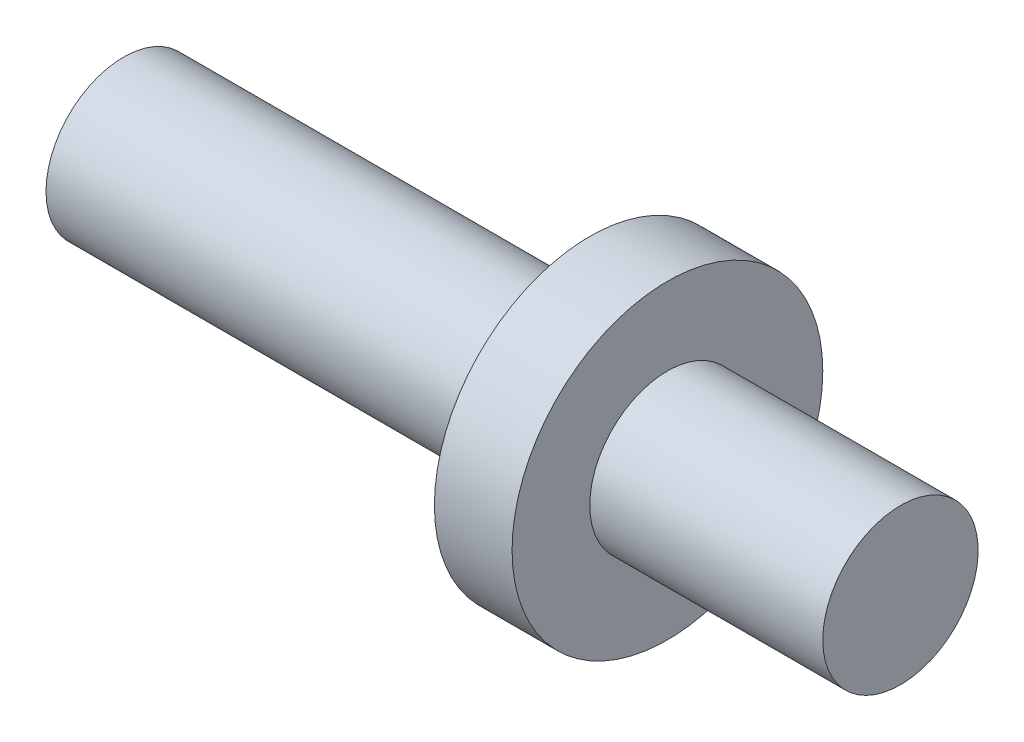
SolidWorks part; units mm, degrees
material "ALUMINUM 6061"
ref_plane "Front Plane" through (0, 0, 0) normal (0, 0, 1) x (1, 0, 0)
ref_plane "Top Plane" through (0, 0, 0) normal (0, 1, 0) x (1, 0, 0)
ref_plane "Right Plane" through (0, 0, 0) normal (1, 0, 0) x (0, 0, -1)
sketch "Sketch1" plane through (0, 0, 0) normal (0, 0, 1) x (1, 0, 0)
  line L0 (0, 0) -> (12.7, 0)
  line L1 (12.7, 0) -> (12.7, 3.175)
  line L2 (12.7, 3.175) -> (3.175, 3.175)
  line L3 (3.175, 3.175) -> (3.175, 6.35)
  line L4 (3.175, 6.35) -> (0, 6.35)
  line L5 (0, 6.35) -> (0, 3.175)
  line L6 (0, 3.175) -> (-19.05, 3.175)
  line L7 (-19.05, 3.175) -> (-19.05, 0)
  line L8 (-19.05, 0) -> (0, 0)
  line L9 (0, 0) -> (0, 3.175) construction
  dimension "D1" = 9.525
  dimension "pinRadius" = 3.175
  dimension "D2" = 19.05
  dimension "D3" = 3.175
  dimension "D4" = 6.35
revolve "Revolve1" add sketch "Sketch1" angle 360 about L8
cosmetic thread "Cosmetic Thread1" parameters "D2"=4.8387
move or copy body "Body-Move/Copy1" [suppressed] bodies to move or copy 101
